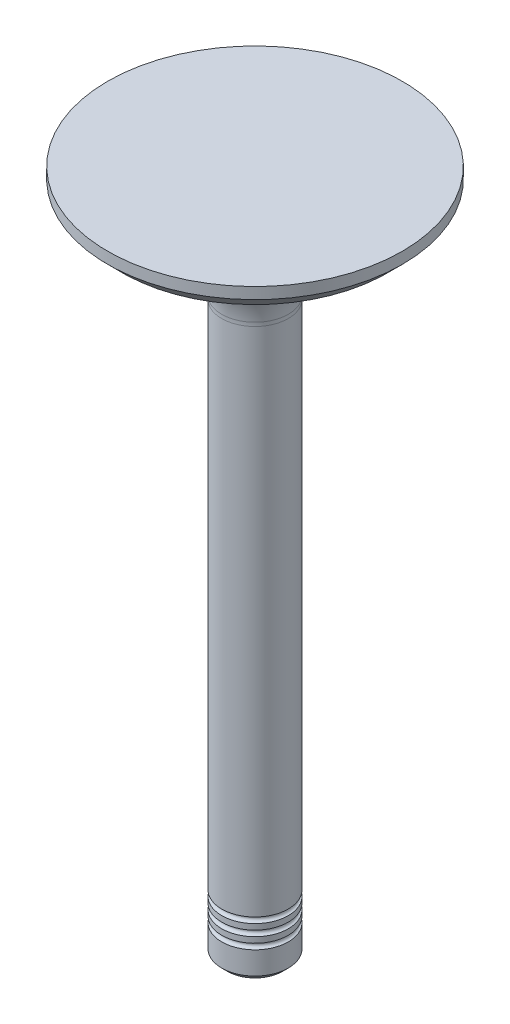
SolidWorks part; units mm, degrees
material "Silchrome I"
ref_plane "Front Plane" through (0, 0, 0) normal (0, 0, 1) x (1, 0, 0)
ref_plane "Top Plane" through (0, 0, 0) normal (0, 1, 0) x (1, 0, 0)
ref_plane "Right Plane" through (0, 0, 0) normal (1, 0, 0) x (0, 0, -1)
sketch "Sketch1" plane through (0, 0, 0) normal (0, 0, 1) x (1, 0, 0)
  line L0 (0, 224.083) -> (0, 103.823) construction
  line L1 (0, 224.083) -> (-25.92, 224.083)
  line L2 (-25.92, 224.083) -> (-25.92, 222.083)
  line L3 (-25.92, 222.083) -> (-23.328, 219.491)
  line L5 (-5.85, 204.053) -> (-5.85, 103.823)
  line L6 (-5.85, 103.823) -> (0, 103.823)
  line L7 (0, 224.083) -> (0, 103.823)
  arc A3 (-23.328, 219.491) -> (-5.85, 204.053) centre (-21.9947, 203.3877) cw
  dimension "D1" = 25.92
  dimension "D2" = 45
  dimension "D4" = 5.85
  dimension "D5" = 18.03
  dimension "D7" = 120.26
  dimension "D3" = 2.592
  dimension "D6" = 2
revolve "Revolve1" add sketch "Sketch1" angle 360 about L0
fillet "Fillet1" radius 10 1 edges at (-5.85, 204.053, 0)
chamfer "Chamfer1" distance 1 angle 45 1 edges at (-5.85, 103.823, 0)
sketch "Sketch5" plane through (0, 0, 0) normal (1, 0, 0) x (0, 0, -1)
  line L1 (-5.85, 203.7983) -> (-5.85, 104.823) construction
  line L3 (-7.48, 111.823) -> (-5.85, 111.823)
  line L4 (0, 203.7983) -> (0, 104.823) construction
  line L5 (5.85, 203.7983) -> (-5.85, 203.7983) construction
  line L6 (5.85, 104.823) -> (-5.85, 104.823) construction
  line L7 (-7.48, 110.823) -> (-5.85, 110.823)
  line L8 (-7.48, 108.823) -> (-5.85, 108.823)
  line L9 (-7.48, 108.823) -> (-7.48, 109.823)
  line L10 (-7.48, 109.823) -> (-5.85, 109.823)
  line L12 (-7.48, 110.823) -> (-7.48, 111.823)
  line L13 (-7.48, 113.823) -> (-5.85, 113.823)
  line L14 (-7.48, 112.823) -> (-5.85, 112.823)
  line L15 (-7.48, 112.823) -> (-7.48, 113.823)
  arc A0 (-5.85, 108.823) -> (-5.85, 109.823) centre (-5.85, 109.323) ccw
  arc A1 (-5.85, 110.823) -> (-5.85, 111.823) centre (-5.85, 111.323) ccw
  arc A2 (-5.85, 112.823) -> (-5.85, 113.823) centre (-5.85, 113.323) ccw
  point P0 (-5.85, 129.583)
  point P10 (-6.85, 109.323)
  dimension "D1" = 1
  dimension "D2" = 1
  dimension "D6" = 4
  dimension "D7" = 6
  dimension "D3" = 3
revolve "Cut-Revolve2" cut sketch "Sketch5" angle 360 about L4
sketch "Sketch6" plane through (0, 0, 0) normal (0, 0, 1) x (1, 0, 0)
  line L0 (0, 224.083) -> (0, 93.6363) construction
  line L1 (25.92, 224.083) -> (-25.92, 224.083) construction
ref_plane "Mating Plane" through (0, 222.083, 0) normal (0, 1, 0) x (1, 0, 0)
equation "\"Valve Diameter\"= 51.84mm"
equation "\"Seat Angle Beta\"= 45deg"
equation "\"Seat Diameter\"= 46.656mm"
equation "\"Stem Diameter\"= 12.96mm"
equation "\"Max Lift\"= 18.03mm"
equation "\"Seat Width\"= 2.592mm"
equation "\"D1@Sketch1\"=\"Valve Diameter\"/2"
equation "\"D2@Sketch1\"=\"Seat Angle Beta\""
equation "\"D5@Sketch1\"=\"Max Lift\""
equation "\"Head Thickness\"= 2mm"
equation "\"Overall Length\"= 120.26mm"
equation "\"D7@Sketch1\"=\"Overall Length\""
equation "\"D3@Sketch1\"=\"Seat Width\""
equation "\"D6@Sketch1\"=\"Head Thickness\""
